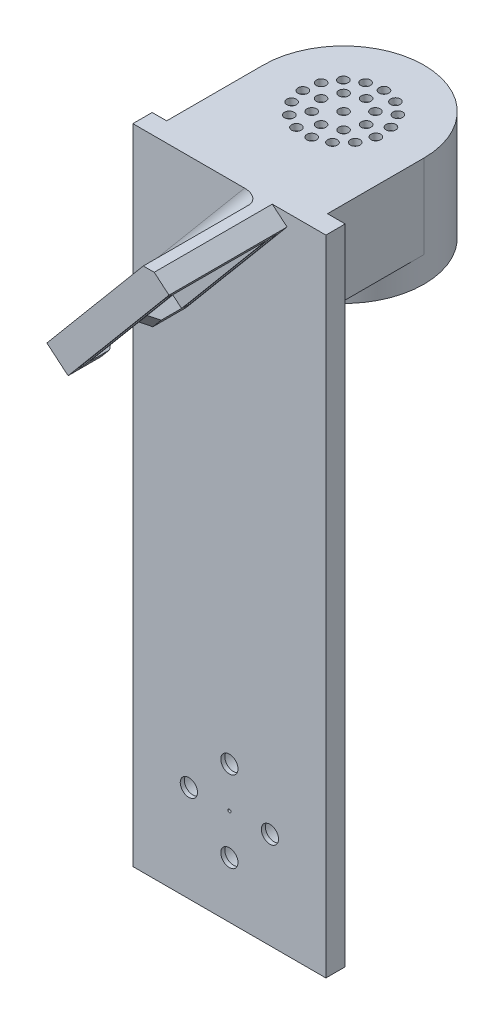
SolidWorks part; units mm, degrees
ref_plane "Front Plane" through (0, 0, 0) normal (0, 0, 1) x (1, 0, 0)
ref_plane "Top Plane" through (0, 0, 0) normal (0, 1, 0) x (1, 0, 0)
ref_plane "Right Plane" through (0, 0, 0) normal (1, 0, 0) x (0, 0, -1)
sketch "Sketch1" plane through (0, 0, 0) normal (0, 1, 0) x (1, 0, 0)
  line L1 (0, 0) -> (38.1, 0)
  line L2 (0, 0) -> (0, 3.81)
  line L4 (38.1, 0) -> (38.1, 3.81)
  line L5 (0, 3.81) -> (38.1, 3.81)
  dimension "D6" = 3.81
  dimension "D1" = 38.1
extrude "main arm" add sketch "Sketch1" along normal blind 127
sketch "Sketch2" plane through (0, 0, 0) normal (0, 0, 1) x (1, 0, 0)
  line L0 (0, 0) -> (38.1, 0) construction
  circle A0 centre (19.05, 19.05) radius 8 construction
  circle A1 centre (19.05, 27.05) radius 1.7
  circle A2 centre (27.05, 19.05) radius 1.7
  circle A3 centre (19.05, 11.05) radius 1.7
  circle A4 centre (11.05, 19.05) radius 1.7
  circle A5 centre (19.05, 19.05) radius 0.3175
  point P3 (19.05, 27.05)
  point P4 (27.05, 19.05)
  point P5 (19.05, 11.05)
  point P6 (11.05, 19.05)
  point P20 (19.05, 0)
  dimension "D1" = 16
  dimension "D2" = 3.4
  dimension "D4" = 0.635
  dimension "D3" = 19.05
extrude "Cut-Extrude1" cut sketch "Sketch2" against normal up to surface (3.81 mm away) up to face at (19.05, 63.5, -3.81)
sketch "Sketch6" plane through (0, 0, -3.81) normal (0, 0, -1) x (-1, 0, 0)
  point P0 (-19.05, 27.05)
  point P4 (-11.05, 19.05)
  point P7 (-19.05, 11.05)
  point P10 (-27.05, 19.05)
hole_wizard "CBORE for M3 SHCS1" positions "Sketch6" profile "Sketch4" counterbore size "M3" standard "ANSI Metric"
sketch "Sketch4" plane through (19.05, 27.05, -3.81) normal (1, 0, 0) x (0, 1, 0)
  line L0 (0, 0) -> (0, 4.8315)
  line L1 (0, 4.8315) -> (1.7, 3.81)
  line L2 (1.7, 3.81) -> (1.7, 3)
  line L3 (1.7, 3) -> (3.25, 3)
  line L5 (3.25, 3) -> (3.25, 0.025)
  line L6 (3.25, 0.025) -> (3.275, 0)
  line L7 (3.275, 0) -> (0, 0)
  line L8 (-3.25, 0.025) -> (-3.275, 0) construction
  line L10 (0, 4.8315) -> (-1.7, 3.81) construction
  line L11 (0, -6.35) -> (0, 107.95) construction
  dimension "Hole Dia." = 3.4
  dimension "Hole Depth" = 3.81
  dimension "C'Bore Dia." = 6.5
  dimension "C'Bore Depth" = 3
  dimension "Near C'Sink Dia." = 6.55
  dimension "Near C'Sink Angle" = 90
  dimension "Drill Angle" = 118
sketch "Sketch8" plane through (0, 127, 0) normal (0, 1, 0) x (1, 0, 0)
  line L0 (2.8575, 22.86) -> (2.8575, 3.81)
  line L1 (38.1, 3.81) -> (0, 3.81) construction
  line L2 (2.8575, 3.81) -> (34.6075, 3.81)
  line L3 (34.6075, 3.81) -> (34.6075, 22.86)
  arc A0 (34.6075, 22.86) -> (2.8575, 22.86) centre (18.7325, 22.86) ccw
  dimension "D1" = 31.75
  dimension "D2" = 19.05
extrude "Boss-Extrude3" add sketch "Sketch8" against normal blind 16.51
sketch "Sketch9" plane through (0, 110.49, 0) normal (0, -1, 0) x (1, 0, 0)
  circle A0 centre (18.7325, -22.86) radius 15.875
  arc A1 (2.8575, -22.86) -> (34.6075, -22.86) centre (18.7325, -22.86) ccw construction
extrude "Boss-Extrude4" add sketch "Sketch9" along normal blind 5.08
sketch "Sketch11" plane through (65.5916, 105.41, -4.2363) normal (0, -1, 0) x (-1, 0, 0)
  circle A2 centre (46.8591, 18.6237) radius 12.7
  circle A3 centre (46.8591, 18.6237) radius 15.875 construction
  dimension "D1" = 25.4
extrude "Cut-Extrude2" cut sketch "Sketch11" against normal blind 20.32
sketch "Sketch13" plane through (0, 127, 127) normal (0, -1, 0) x (-1, 0, 0)
  circle A2 centre (-18.7325, 149.86) radius 4.445 construction
  circle A3 centre (-18.7325, 154.305) radius 0.9525
  circle A4 centre (-15.5894, 153.0031) radius 0.9525
  circle A5 centre (-14.2875, 149.86) radius 0.9525
  circle A6 centre (-15.5894, 146.7169) radius 0.9525
  circle A7 centre (-18.7325, 145.415) radius 0.9525
  circle A8 centre (-21.8756, 146.7169) radius 0.9525
  circle A9 centre (-18.7325, 149.86) radius 7.62 construction
  circle A10 centre (-19.0969, 157.4713) radius 0.9525
  circle A11 centre (-15.9696, 156.9615) radius 0.9525
  circle A12 centre (-13.32, 155.2237) radius 0.9525
  circle A13 centre (-11.6063, 152.5586) radius 0.9525
  circle A14 centre (-11.1248, 149.4268) radius 0.9525
  circle A15 centre (-11.9587, 146.3699) radius 0.9525
  circle A16 centre (-18.7325, 149.86) radius 0.9525
  circle A17 centre (-13.9639, 143.9165) radius 0.9525
  circle A18 centre (-16.7936, 142.4908) radius 0.9525
  circle A19 centre (-19.9585, 142.3393) radius 0.9525
  circle A20 centre (-22.9115, 143.4882) radius 0.9525
  circle A21 centre (-25.1419, 145.7388) radius 0.9525
  circle A22 centre (-26.264, 148.702) radius 0.9525
  circle A23 centre (-26.0839, 151.8655) radius 0.9525
  circle A24 centre (-24.6326, 154.6821) radius 0.9525
  circle A25 centre (-22.1612, 156.665) radius 0.9525
  circle A26 centre (-23.1775, 149.86) radius 0.9525
  circle A27 centre (-21.8756, 153.0031) radius 0.9525
  circle A30 centre (-18.7325, 149.86) radius 15.875 construction
  point P21 (-18.7325, 149.86)
  point P35 (-18.7325, 149.86)
  dimension "D1" = 8.89
  dimension "D2" = 1.905
  dimension "D4" = 15.24
  dimension "D5" = 1.905
  dimension "D7" = 1.905
  dimension "D3" = 8
  dimension "D6" = 15
extrude "Cut-Extrude3" cut sketch "Sketch13" against normal up to surface (-1.27 mm away) up to face at (18.7325, 125.73, -35.56)
thread "Thread1" pitch 2.54 method cut profile "Thread Profile1" start angle 0, offset 2.54, length 19.05, pitch 2.2087, diameter 25.4
ref_plane "Plane1" through (31.4325, 102.87, -22.86) normal (0, 0, 1) x (1, 0, 0)
sketch "Thread Profile1" plane through (31.4325, 102.87, -22.86) normal (0, 0, 1) x (1, 0, 0)
  line L0 (0, 0) -> (0, 2.54) construction
  line L1 (0, 0) -> (1.3748, 0.7937)
  line L2 (1.3748, 0.7937) -> (1.3748, 1.1112)
  line L3 (1.3748, 1.1112) -> (0, 1.905)
  line L4 (1.3748, 0.9525) -> (0, 0.9525) construction
  line L11 (0, 0) -> (0, 1.905)
  point P2 (0, 0)
  dimension "Pitch" = 2.54
  dimension "Profile_Angle" = 60
  dimension "Profile_Land" = 0.3175
  dimension "Profile_Height" = 1.3748
sketch "Sketch14" plane through (0, 0, 0) normal (0, 0, 1) x (1, 0, 0)
  line L0 (25.3633, 127) -> (6.3351, 104.3231)
  line L2 (0, 127) -> (0, 0) construction
  line L3 (6.3351, 104.3231) -> (7.5998, 103.2618)
  line L4 (7.5998, 103.2618) -> (27.5185, 127)
  line L7 (27.5185, 127) -> (25.3633, 127)
  line L8 (0, 127) -> (38.1, 127) construction
  dimension "D1" = 1.651
  dimension "D2" = 40
  dimension "D3" = 30.988
extrude "Boss-Extrude5" add sketch "Sketch14" along normal blind 23.3045
sketch "Sketch15" plane through (-46.3868, 38.9231, 0) normal (0.766, -0.6428, 0) x (0.6428, 0.766, 0)
  line L1 (83.9882, 0) -> (114.9762, 0)
  line L2 (83.9882, 0) -> (83.9882, 23.3045)
  line L3 (83.9882, 23.3045) -> (114.9762, 23.3045)
  line L4 (114.9762, 0) -> (114.9762, 23.3045)
  line L5 (86.5282, 2.54) -> (112.4362, 2.54)
  line L6 (86.5282, 2.54) -> (86.5282, 20.7645)
  line L7 (86.5282, 20.7645) -> (112.4362, 20.7645)
  line L8 (112.4362, 2.54) -> (112.4362, 20.7645)
  dimension "D1" = 2.54
  dimension "D2" = 18.2245
  dimension "D3" = 2.54
  dimension "D4" = 2.54
extrude "Boss-Extrude6" add sketch "Sketch15" along normal blind 3.81
sketch "Sketch16" plane through (-46.3868, 38.9231, 0) normal (0.766, -0.6428, 0) x (0.6428, 0.766, 0)
  line L1 (86.5282, 20.7645) -> (90.3382, 20.7645)
  line L2 (86.5282, 20.7645) -> (86.5282, 16.9545)
  line L3 (86.5282, 16.9545) -> (90.3382, 16.9545)
  line L4 (90.3382, 20.7645) -> (90.3382, 16.9545)
  line L5 (86.5282, 2.54) -> (90.3382, 2.54)
  line L6 (86.5282, 2.54) -> (86.5282, 6.35)
  line L7 (86.5282, 6.35) -> (90.3382, 6.35)
  line L8 (90.3382, 2.54) -> (90.3382, 6.35)
  line L9 (112.4362, 2.54) -> (108.6262, 2.54)
  line L10 (112.4362, 2.54) -> (112.4362, 6.35)
  line L11 (112.4362, 6.35) -> (108.6262, 6.35)
  line L12 (108.6262, 2.54) -> (108.6262, 6.35)
  line L13 (112.4362, 20.7645) -> (108.6262, 20.7645)
  line L14 (112.4362, 20.7645) -> (112.4362, 16.9545)
  line L15 (112.4362, 16.9545) -> (108.6262, 16.9545)
  line L16 (108.6262, 20.7645) -> (108.6262, 16.9545)
  dimension "D1" = 3.81
extrude "Boss-Extrude7" add sketch "Sketch16" along normal blind 1.27
sketch "Sketch17" plane through (-46.3868, 38.9231, 0) normal (0.766, -0.6428, 0) x (0.6428, 0.766, 0)
  line L0 (83.9882, 23.3045) -> (114.9762, 23.3045) construction
  line L1 (99.4822, 20.7645) -> (99.4822, 2.54) construction
  line L2 (108.6262, 20.7645) -> (90.3382, 20.7645) construction
  line L3 (86.5282, 2.54) -> (112.4362, 2.54) construction
  line L4 (90.3382, 2.54) -> (108.6262, 2.54) construction
  circle A0 centre (99.4822, 11.6523) radius 5.0165
  point P15 (99.4822, 23.3045)
  dimension "D1" = 10.033
extrude "Cut-Extrude4" cut sketch "Sketch17" against normal up to surface (1.651 mm away) up to face at (15.8492, 115.6615, 11.6522)
sketch "Sketch18" plane through (53.9866, 64.3387, 0) normal (-0.6428, -0.766, 0) x (0, 0, 1)
  line L0 (6.5722, 56.7436) -> (16.7323, 56.7436)
  line L1 (23.3045, 56.7436) -> (0, 56.7436) construction
  line L2 (16.7323, 56.7436) -> (13.5572, 59.9186)
  line L3 (13.5572, 59.9186) -> (9.7472, 59.9186)
  line L4 (9.7472, 59.9186) -> (6.5722, 56.7436)
  line L5 (0, 56.7436) -> (23.3045, 56.7436) construction
  point P10 (11.6522, 56.7436)
  dimension "D1" = 10.16
  dimension "D2" = 3.81
  dimension "D3" = 45
  dimension "D4" = 45
extrude "Cut-Extrude5" cut sketch "Sketch18" against normal up to surface (2.54 mm away) up to face at (10.4486, 104.1871, 11.6522)
sketch "Sketch19" plane through (-43.4681, 36.4741, 0) normal (0.766, -0.6428, 0) x (0, 0, -1)
  line L0 (-22.0345, 112.5632) -> (-22.0345, 86.4012) construction
  line L1 (-21.3995, 112.5632) -> (-21.3995, 86.4012)
  line L2 (-22.6695, 112.5632) -> (-22.6695, 86.4012)
  line L3 (-1.27, 112.5632) -> (-1.27, 86.4012) construction
  line L4 (-0.635, 112.5632) -> (-0.635, 86.4012)
  line L5 (-1.905, 112.5632) -> (-1.905, 86.4012)
  line L6 (-23.3045, 114.9762) -> (-23.3045, 83.9882) construction
  line L7 (0, 83.9882) -> (0, 114.9762) construction
  line L8 (0, 114.9762) -> (-23.3045, 114.9762) construction
  line L9 (-23.3045, 83.9882) -> (-16.7323, 83.9882) construction
  line L10 (-6.5723, 83.9882) -> (0, 83.9882) construction
  arc A0 (-21.3995, 112.5632) -> (-22.6695, 112.5632) centre (-22.0345, 112.5632) ccw
  arc A1 (-22.6695, 86.4012) -> (-21.3995, 86.4012) centre (-22.0345, 86.4012) ccw
  arc A2 (-0.635, 112.5632) -> (-1.905, 112.5632) centre (-1.27, 112.5632) ccw
  arc A3 (-1.905, 86.4012) -> (-0.635, 86.4012) centre (-1.27, 86.4012) ccw
  point P2 (-22.0345, 99.4822)
  point P7 (-1.27, 99.4822)
  dimension "D1" = 0.635
  dimension "D2" = 0.635
  dimension "D3" = 1.27
  dimension "D4" = 1.27
  dimension "D5" = 2.413
  dimension "D6" = 2.413
  dimension "D7" = 2.413
  dimension "D8" = 2.413
  dimension "D9" = 20.7645
extrude "Cut-Extrude6" cut sketch "Sketch19" against normal blind 2.794
fillet "Fillet1" radius 2.54 1 edges at (15.8492, 115.6615, 0)
equation "\"wall thickness\"=0.15"
equation "\"D1@Boss-Extrude3\"=.65"
equation "\"D6@Sketch1\"=\"wall thickness\""
